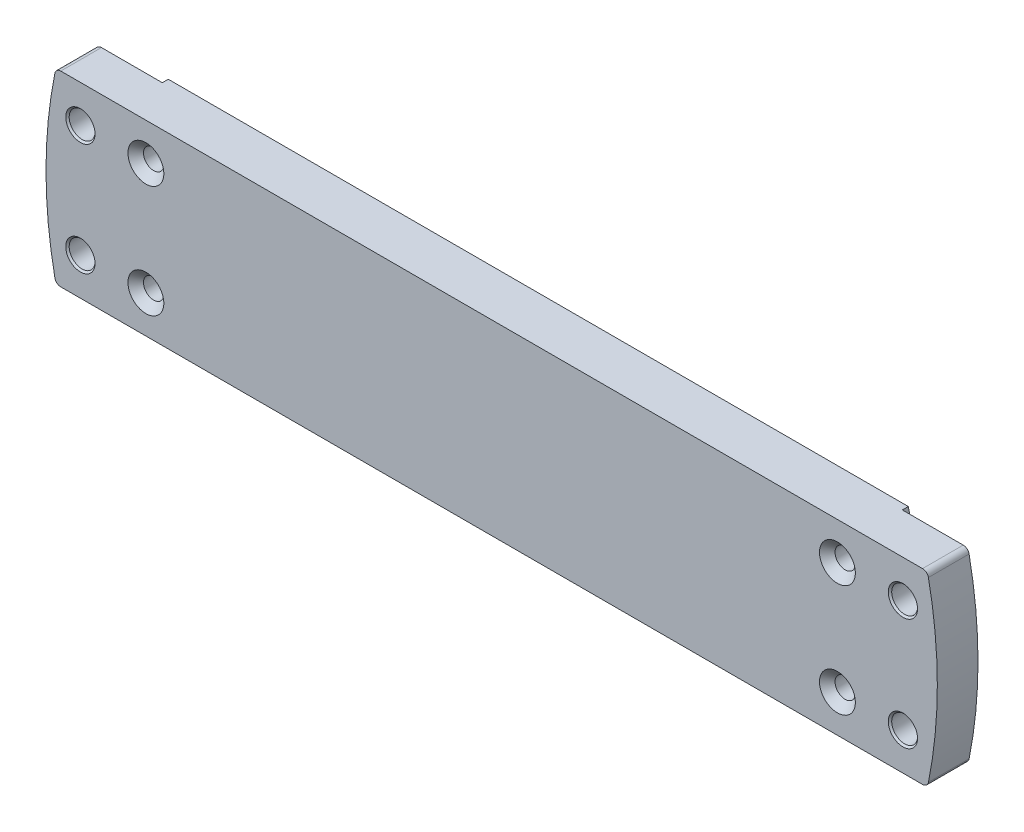
SolidWorks part; units mm, degrees
note: '?' marks a value the reader was unsure of.
ref_plane "Front Plane" through (0, 0, 0) normal (0, 0, 1) x (1, 0, 0)
ref_plane "Top Plane" through (0, 0, 0) normal (0, 1, 0) x (1, 0, 0)
ref_plane "Right Plane" through (0, 0, 0) normal (1, 0, 0) x (0, 0, -1)
ref_axis "Axis1" through (0, 0, -47.0257) along (0, 0, 1)?
sketch "Sketch1" plane through (0, 0, 0) normal (0, 0, -1) x (1, 0, 0)
  line L0 (19.304, -15.875) -> (19.304, -9.525) construction
  line L1 (19.304, -9.525) -> (4.445, -9.525) construction
  line L2 (74.0085, -15.875) -> (-74.0085, -15.875)
  line L3 (4.445, -9.525) -> (4.445, 0) construction
  line L4 (74.0085, 15.875) -> (-74.0085, 15.875)
  line L5 (0, 35.2641) -> (0, 51.0808) construction
  line L7 (-19.304, -15.875) -> (-19.304, -9.525) construction
  line L8 (-19.304, -9.525) -> (-4.445, -9.525) construction
  line L9 (-4.445, -9.525) -> (-4.445, 0) construction
  arc A0 (-74.0085, 15.875) -> (-74.0085, -15.875) centre (0, 0) ccw
  arc A1 (4.445, 0) -> (-4.445, 0) centre (0, 0) ccw construction
  arc A2 (74.0085, 15.875) -> (74.0085, -15.875) centre (0, 0) cw
  dimension "D1" = 15.875
  dimension "D2" = 75.692
  dimension "D3" = 15.875
  dimension "D4" = 9.525
  dimension "D5" = 19.304
  dimension "D6" = 8.89
extrude "Boss-Extrude1" add sketch "Sketch1" against normal blind 7.9248
sketch "Sketch12" plane through (0, 0, 0) normal (0, 1, 0) x (1, 0, 0)
  line L0 (0, 12.4849) -> (0, 60.1189) construction
  line L1 (64.8208, 34.544) -> (100.3808, 34.544)
  line L2 (64.8208, 34.544) -> (64.8208, -1.016)
  line L3 (64.8208, -1.016) -> (100.3808, -1.016)
  line L4 (100.3808, 34.544) -> (100.3808, -1.016)
  dimension "D1" = 1.016
  dimension "D2" = 129.6416
  dimension "D3" = 35.56
  dimension "D4" = 35.56
revolve "Cut-Revolve1" cut sketch "Sketch12" angle 360 about L0
fillet "Fillet1" radius 1.016 4 edges at (-74.0085, 15.875, 4.4704) (-74.0085, -15.875, 4.4704) (74.0085, 15.875, 4.4704) (74.0085, -15.875, 4.4704)
hole_wizard "#8-32 Tapped Hole2" positions "Sketch3" profile "Sketch2" tap size "#8-32" standard "ANSI Inch" end condition through all
sketch "Sketch3" plane through (0, 0, 0) normal (0, 0, -1) x (-1, 0, 0)
  point P0 (58.7248, 9.525)
  point P2 (58.7248, -9.525)
  point P4 (-58.7248, 9.525)
  point P6 (-58.7248, -9.525)
  dimension "D1" = 9.525
  dimension "D2" = 9.525
  dimension "D3" = 58.7248
  dimension "D4" = 58.7248
sketch "Sketch2" plane through (-58.7248, 9.525, 0) normal (1, 0, 0) x (0, 1, 0)
  line L0 (0, 0) -> (0, 7.9248)
  line L1 (0, 7.9248) -> (3.048, 7.9248)
  line L2 (1.7272, 6.604) -> (1.7272, 0.5588)
  line L3 (1.7272, 0.5588) -> (2.286, 0)
  line L5 (2.286, 0) -> (0, 0)
  line L6 (-1.7272, 0.5588) -> (-2.286, 0) construction
  line L7 (3.048, 7.9248) -> (1.7272, 6.604)
  line L8 (-3.048, 7.9248) -> (-1.7272, 6.604) construction
  line L11 (0, -6.35) -> (0, 107.95) construction
  dimension "Thru Tap Drill Dia." = 3.4544
  dimension "Thru Tap Drill Depth" = 7.9248
  dimension "Near C'Sink Dia." = 4.572
  dimension "Near C'Sink Angle" = 90
  dimension "Far C'Sink Dia." = 6.096
  dimension "Far C'Sink Angle" = 90
cosmetic thread "Hole Thread11" parameters "D2"=4.1656
cosmetic thread "Hole Thread12" parameters "D2"=4.1656
cosmetic thread "Hole Thread13" parameters "D2"=4.1656
cosmetic thread "Hole Thread14" parameters "D2"=4.1656
hole_wizard "#17 (0.173) Diameter Hole1" positions "Sketch6" profile "Sketch5" hole size "#17" standard "ANSI Inch" end condition up to next
sketch "Sketch6" plane through (0, 0, 7.9248) normal (0, 0, 1) x (1, 0, 0)
  point P0 (69.85, 9.525)
  point P2 (69.85, -9.525)
  point P4 (-69.85, 9.525)
  point P6 (-69.85, -9.525)
  dimension "D1" = 9.525
  dimension "D2" = 19.05
  dimension "D3" = 69.85
  dimension "D4" = 69.85
sketch "Sketch5" plane through (69.85, 9.525, 7.9248) normal (1, 0, 0) x (0, -1, 0)
  line L0 (0, 0) -> (0, 6.9088)
  line L1 (0, 6.9088) -> (2.4892, 6.9088)
  line L2 (2.1971, 6.6167) -> (2.1971, 0.2921)
  line L3 (2.1971, 0.2921) -> (2.4892, 0)
  line L5 (2.4892, 0) -> (0, 0)
  line L6 (-2.1971, 0.2921) -> (-2.4892, 0) construction
  line L7 (2.4892, 6.9088) -> (2.1971, 6.6167)
  line L8 (-2.4892, 6.9088) -> (-2.1971, 6.6167) construction
  line L11 (0, -6.35) -> (0, 107.95) construction
  dimension "Thru Hole Dia." = 4.3942
  dimension "Thru Hole Depth" = 6.9088
  dimension "Near C'Sink Dia." = 4.9784
  dimension "Near C'Sink Angle" = 90
  dimension "Far C'Sink Dia." = 4.9784
  dimension "Far C'Sink Angle" = 90
hole_wizard "#8-32 Tapped Hole3" [suppressed] positions "Sketch11" profile "Sketch10" tap size "#8-32" standard "ANSI Inch"
sketch "Sketch11" plane through (0, 0, 7.9248) normal (0, 0, 1) x (1, 0, 0)
  point P0 (38.1, 9.525)
  point P2 (38.1, -9.525)
  point P4 (-38.1, 9.525)
  point P6 (-38.1, -9.525)
  dimension "D1" = 38.1
  dimension "D2" = 38.1
  dimension "D3" = 9.525
  dimension "D4" = 9.525
sketch "Sketch10" plane through (38.1, 9.525, 7.9248) normal (1, 0, 0) x (0, -1, 0)
  line L0 (0, 0) -> (0, 7.9248)
  line L1 (0, 7.9248) -> (1.7272, 7.9248)
  line L2 (1.7272, 7.9248) -> (1.7272, 0)
  line L5 (1.7272, 0) -> (0, 0)
  line L11 (0, -6.35) -> (0, 107.95) construction
  dimension "Thru Tap Drill Dia." = 3.4544
  dimension "Thru Tap Drill Depth" = 7.9248
cosmetic thread "Hole Thread7" [suppressed] parameters "D2"=4.1656
cosmetic thread "Hole Thread8" [suppressed] parameters "D2"=4.1656
cosmetic thread "Hole Thread9" [suppressed] parameters "D2"=4.1656
cosmetic thread "Hole Thread10" [suppressed] parameters "D2"=4.1656
sketch "Sketch13" [suppressed] plane through (0, 0, 1.016) normal (0, 0, -1) x (-1, 0, 0)
  line L0 (-73.1828, 15.875) -> (-64.4494, 15.875)
  line L2 (-62.9254, 15.875) -> (-73.1828, 15.875) construction
  line L5 (-73.1828, -15.875) -> (-62.9254, -15.875) construction
  line L6 (-64.4494, -15.875) -> (-73.1828, -15.875)
  arc A0 (-74.1784, 15.0612) -> (-74.1784, -15.0612) centre (0, 0) ccw construction
  arc A1 (-74.1784, 15.0612) -> (-74.1784, -15.0612) centre (0, 0) ccw
  arc A2 (-74.1784, -15.0612) -> (-73.1828, -15.875) centre (-73.1828, -14.859) ccw construction
  arc A3 (-73.1828, 15.875) -> (-74.1784, 15.0612) centre (-73.1828, 14.859) ccw construction
  arc A4 (-74.1784, -15.0612) -> (-73.1828, -15.875) centre (-73.1828, -14.859) ccw
  arc A5 (-73.1828, 15.875) -> (-74.1784, 15.0612) centre (-73.1828, 14.859) ccw
  dimension "D1" = 1.524
sketch "Sketch14" [suppressed] plane through (0, 0, 1.016) normal (0, 0, -1) x (-1, 0, 0)
  line L0 (73.1828, 15.875) -> (64.4494, 15.875)
  line L2 (73.1828, 15.875) -> (62.9254, 15.875) construction
  line L5 (62.9254, -15.875) -> (73.1828, -15.875) construction
  line L6 (64.4494, -15.875) -> (73.1828, -15.875)
  arc A0 (74.1784, -15.0612) -> (74.1784, 15.0612) centre (0, 0) ccw construction
  arc A1 (74.1784, -15.0612) -> (74.1784, 15.0612) centre (0, 0) ccw
  arc A2 (74.1784, 15.0612) -> (73.1828, 15.875) centre (73.1828, 14.859) ccw construction
  arc A3 (73.1828, -15.875) -> (74.1784, -15.0612) centre (73.1828, -14.859) ccw construction
  arc A4 (74.1784, 15.0612) -> (73.1828, 15.875) centre (73.1828, 14.859) ccw
  arc A5 (73.1828, -15.875) -> (74.1784, -15.0612) centre (73.1828, -14.859) ccw
  dimension "D1" = 1.524
